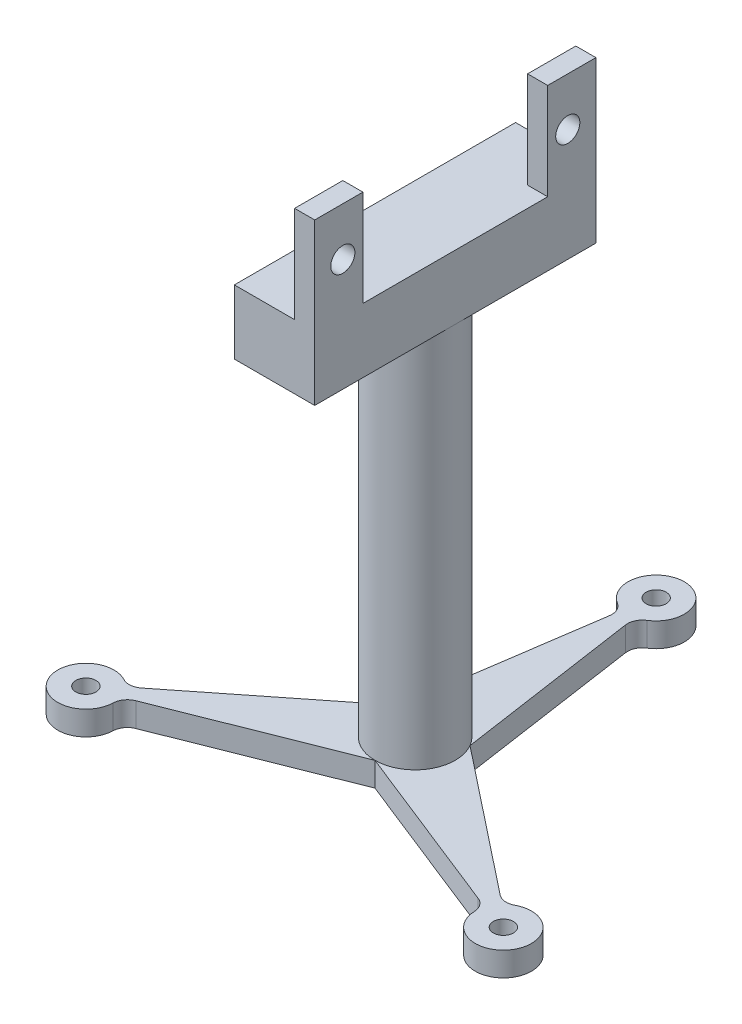
SolidWorks part; units mm, degrees
ref_plane "Front Plane" through (0, 0, 0) normal (0, 0, 1) x (1, 0, 0)
ref_plane "Top Plane" through (0, 0, 0) normal (0, 1, 0) x (1, 0, 0)
ref_plane "Right Plane" through (0, 0, 0) normal (1, 0, 0) x (0, 0, -1)
sketch "Sketch1" plane through (0, 0, 0) normal (0, 0, 1) x (1, 0, 0)
  line L0 (0, 0) -> (0, 50)
  line L1 (0, 50) -> (5, 50)
  line L2 (5, 50) -> (5, 0)
  line L3 (5, 0) -> (0, 0)
  dimension "D1" = 50
  dimension "D2" = 5
revolve "Revolve1" add sketch "Sketch1" angle 360 about L0
sketch "Sketch2" plane through (0, 0, 0) normal (0, 1, 0) x (1, 0, 0)
  line L0 (-4.3301, 2.5) -> (4.3301, 2.5)
  line L1 (4.3301, 2.5) -> (0, -5)
  line L2 (0, -5) -> (-4.3301, 2.5)
  line L3 (-4.3301, 2.5) -> (-1, 25.1833)
  line L4 (4.3301, 2.5) -> (1, 25.1833)
  circle A0 centre (0, 0) radius 5 construction
  arc A1 (-1, 25.1833) -> (-1.855, 27.032) centre (-2.8415, 25.4537) ccw
  arc A2 (1, 25.1833) -> (1.855, 27.032) centre (2.8415, 25.4537) cw
  arc A3 (1.855, 27.032) -> (-1.855, 27.032) centre (0, 30) ccw
  circle A4 centre (0, 30) radius 1.25
  dimension "D2" = 7
  dimension "D3" = 2.5
  dimension "D5" = 2
  dimension "D1" = 30
  dimension "D4" = 3.7101
extrude "Boss-Extrude1" add sketch "Sketch2" along normal blind 3 contours A2 A3 A1 L3 L0 L4 A4 region at (0, 0, -15.7105)
pattern_circular "CirPattern1" count 3 over 360 about axis through (0, 50, 0) along (0, -1, 0) of "Boss-Extrude1"
sketch "Sketch3" plane through (0, 0, 0) normal (1, 0, 0) x (0, 0, -1)
  line L0 (17.5, 50) -> (-17.5, 50)
  line L1 (-17.5, 50) -> (-17.5, 70)
  line L2 (-17.5, 70) -> (-11.5, 70)
  line L3 (-11.5, 70) -> (-11.5, 58)
  line L4 (-11.5, 58) -> (11.5, 58)
  line L5 (11.5, 58) -> (11.5, 70)
  line L6 (11.5, 70) -> (17.5, 70)
  line L7 (17.5, 70) -> (17.5, 50)
  line L8 (5, 50) -> (-5, 50) construction
  line L9 (-11.5, 58) -> (-17.5, 58)
  line L10 (11.5, 58) -> (17.5, 58)
  circle A0 centre (-14, 64) radius 1.5
  circle A1 centre (14, 64) radius 1.5
  point P2 (0, 50)
  point P9 (0, 58)
  dimension "D7" = 2.5
  dimension "5" = 3
  dimension "D1" = 35
  dimension "D2" = 23
  dimension "D3" = 20
  dimension "D4" = 20
  dimension "D5" = 12
  dimension "D6" = 6
  dimension "D8" = 2.5
extrude "Boss-Extrude2" add sketch "Sketch3" along normal blind 5 and the other way blind 5 contours L10 L4 L9 L1 L0 L7 region at (0, 54, 0)
extrude "Boss-Extrude3" add sketch "Sketch3<3>" along normal blind 5 contours L9 L3 L2 L1 A0 | L5 L10 L7 L6 A1 region at (0, 58.1342, -14.5) region at (0, 64, 17.3658)
sketch "Sketch3<3>" plane through (0, 0, 0) normal (1, 0, 0) x (0, 0, -1) same geometry as "Sketch3"
sketch "Sketch4" plane through (0, 0, 17.5) normal (0, 0, 1) x (1, 0, 0)
  line L0 (0, 58) -> (2.5, 58)
  line L1 (2.5, 58) -> (2.5, 70)
  line L2 (5, 70) -> (0, 70) construction
  line L3 (2.5, 70) -> (0, 70)
  line L4 (0, 70) -> (0, 58)
extrude "Cut-Extrude1" cut sketch "Sketch4" against normal through all
sketch "Sketch5" plane through (5, 0, 0) normal (1, 0, 0) x (0, 0, -1)
